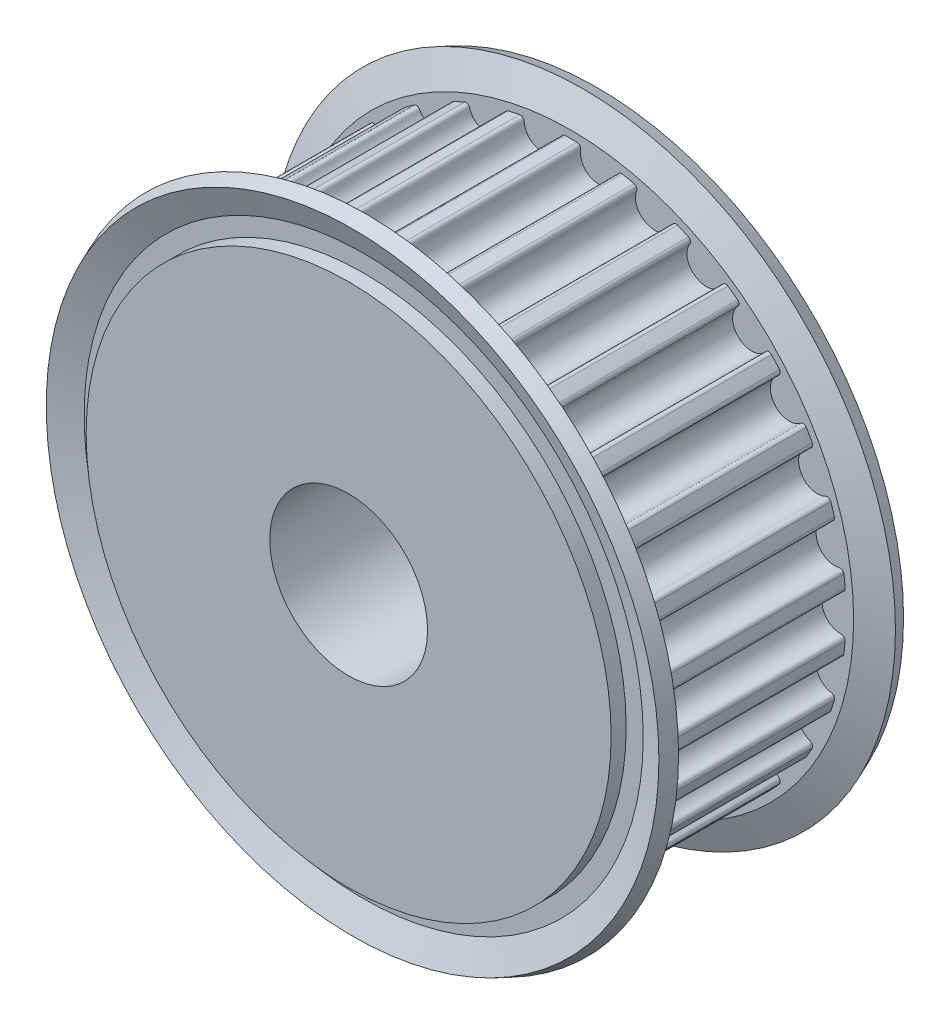
SolidWorks part; units mm, degrees
ref_plane "前视基准面" through (0, 0, 0) normal (0, 0, 1) x (1, 0, 0)
ref_plane "上视基准面" through (0, 0, 0) normal (0, 1, 0) x (1, 0, 0)
ref_plane "右视基准面" through (0, 0, 0) normal (1, 0, 0) x (0, 0, -1)
ref_axis "基准轴1" through (0, 0, 55) along (0, 0, -1)
sketch "SketchRevolveGearBelt01Pulley" plane through (0, 0, 0) normal (1, 0, 0) x (0, 0, -1)
  line L0 (0, 0) -> (1, 0) construction
  line L1 (6.4008, 0) -> (6.4008, 13.3069)
  line L2 (6.4008, 13.3069) -> (5.6388, 13.3069)
  line L3 (5.6388, 13.3069) -> (5.6388, 14.1713)
  line L4 (5.6388, 14.1713) -> (6.2015, 15.5299)
  line L5 (6.2015, 15.5299) -> (5.4975, 15.8215)
  line L6 (5.4975, 15.8215) -> (4.8768, 14.3229)
  line L7 (4.8768, 14.3229) -> (4.8768, 13.9419)
  line L8 (4.8768, 13.9419) -> (-4.8768, 13.9419)
  line L9 (-4.8768, 13.9419) -> (-4.8768, 14.3229)
  line L10 (-4.8768, 14.3229) -> (-5.4975, 15.8215)
  line L11 (-5.4975, 15.8215) -> (-6.2015, 15.5299)
  line L12 (-6.2015, 15.5299) -> (-5.6388, 14.1713)
  line L13 (-5.6388, 14.1713) -> (-5.6388, 13.3069)
  line L14 (-5.6388, 13.3069) -> (-6.4008, 13.3069)
  line L15 (-6.4008, 13.3069) -> (-6.4008, 0)
  line L16 (-6.4008, 0) -> (6.4008, 0)
  dimension "GearBeltFlange1OutsideLength" = 0.8644
  dimension "GearBeltFlange1X" = 0.5627
  dimension "GearBeltFlange1Y" = 1.3586
  dimension "GearBeltFlangeThickness" = 0.762
  dimension "GearBeltFlangeInside" = 0.381
  dimension "GearBeltOutsideDiameter" = 13.9419
  dimension "GearBeltFlange2X" = 0.5627
revolve "GearBelt01Pulley" add sketch "SketchRevolveGearBelt01Pulley" angle 360 about L0
sketch "SketchToothGearBelt01Pulley" plane through (0, 0, 0) normal (0, 0, 1) x (1, 0, 0)
  arc A0 (13.8935, 1.162) -> (13.8935, -1.162) centre (0, 0) cw
  spline S0 degree 3 poles (13.8935, -1.162) (13.8944, -1.1516) (13.8944, -1.1357) (13.8918, -1.1148) (13.8886, -1.0994) (13.8841, -1.0843) (13.8784, -1.0695) (13.8714, -1.0553) (13.8634, -1.0418) (13.8542, -1.0289) (13.844, -1.0168) (13.8329, -1.0057) (13.8209, -0.9954) (13.808, -0.9862) (13.7945, -0.9781) (13.7803, -0.9712) (13.7656, -0.9654) (13.7505, -0.9609) (13.735, -0.9576) (13.7194, -0.9556) (13.6903, -0.9547) (13.6423, -0.9556) (13.5752, -0.953) (13.503, -0.9442) (13.4317, -0.9299) (13.3617, -0.91) (13.2935, -0.8847) (13.2275, -0.8541) (13.1641, -0.8184) (13.1036, -0.7779) (13.0466, -0.7328) (12.9932, -0.6834) (12.9439, -0.6299) (12.8989, -0.5727) (12.8585, -0.5122) (12.8231, -0.4487) (12.7926, -0.3826) (12.7675, -0.3143) (12.7478, -0.2443) (12.7336, -0.1729) (12.725, -0.1007) (12.7231, -0.0476) (12.7232, -0.014) (12.7232, 0) (12.7232, 0.014) (12.7231, 0.0476) (12.725, 0.1007) (12.7336, 0.1729) (12.7478, 0.2443) (12.7675, 0.3143) (12.7926, 0.3826) (12.8231, 0.4487) (12.8585, 0.5122) (12.8989, 0.5727) (12.9439, 0.6299) (12.9932, 0.6834) (13.0466, 0.7328) (13.1036, 0.7779) (13.1641, 0.8184) (13.2275, 0.8541) (13.2935, 0.8847) (13.3617, 0.91) (13.4317, 0.9299) (13.503, 0.9442) (13.5752, 0.953) (13.6423, 0.9556) (13.6903, 0.9547) (13.7194, 0.9556) (13.735, 0.9576) (13.7505, 0.9609) (13.7656, 0.9654) (13.7803, 0.9712) (13.7945, 0.9781) (13.808, 0.9862) (13.8209, 0.9954) (13.8329, 1.0057) (13.844, 1.0168) (13.8542, 1.0289) (13.8634, 1.0418) (13.8714, 1.0553) (13.8784, 1.0695) (13.8841, 1.0843) (13.8886, 1.0994) (13.8918, 1.1148) (13.8944, 1.1357) (13.8944, 1.1516) (13.8935, 1.162) knots 0 0 0 0 0.008513 0.012769 0.017025 0.021281 0.025538 0.029794 0.03405 0.038306 0.042563 0.046819 0.051075 0.055331 0.059588 0.063844 0.0681 0.072356 0.076613 0.080869 0.085125 0.100157 0.119771 0.139386 0.159 0.178614 0.198229 0.217843 0.237457 0.257071 0.276686 0.2963 0.315914 0.335529 0.355143 0.374757 0.394372 0.413986 0.4336 0.453214 0.472829 0.492443 0.496222 0.5 0.503778 0.507557 0.527171 0.546786 0.5664 0.586014 0.605628 0.625243 0.644857 0.664471 0.684086 0.7037 0.723314 0.742929 0.762543 0.782157 0.801771 0.821386 0.841 0.860614 0.880229 0.899843 0.914875 0.919131 0.923387 0.927644 0.9319 0.936156 0.940412 0.944669 0.948925 0.953181 0.957437 0.961694 0.96595 0.970206 0.974462 0.978719 0.982975 0.987231 0.991487 1 1 1 1
extrude "ToothExtrudeCutGearBelt01Pulley" cut sketch "SketchToothGearBelt01Pulley" against normal blind 4.8768 and the other way blind 4.8768
pattern_circular "PatternGearBelt01Pulley" count 30 every 12 about axis through (0, 0, 55) along (0, 0, -1) of "ToothExtrudeCutGearBelt01Pulley"
sketch "BoreRevolveSketch" plane through (0, 0, 0) normal (1, 0, 0) x (0, 0, -1)
  line L0 (0, 0) -> (1, 0) construction
  line L1 (-6.4008, 0) -> (6.4008, 0)
  line L2 (6.4008, 0) -> (6.4008, 4)
  line L3 (6.4008, 4) -> (-6.4008, 4)
  line L4 (-6.4008, 4) -> (-6.4008, 0)
  dimension "TaperSide1" = 4
  dimension "TaperSide2" = 4
revolve "BoreRevolveCut" cut sketch "BoreRevolveSketch" angle 360 about L0
sketch "AuxiliarySketchGearBelt01Pulley" plane through (0, 0, 0) normal (0, 0, 1) x (1, 0, 0)
  circle A0 centre (0, 0) radius 14.3229 construction
  dimension "PitchDiameter" = 28.6458
